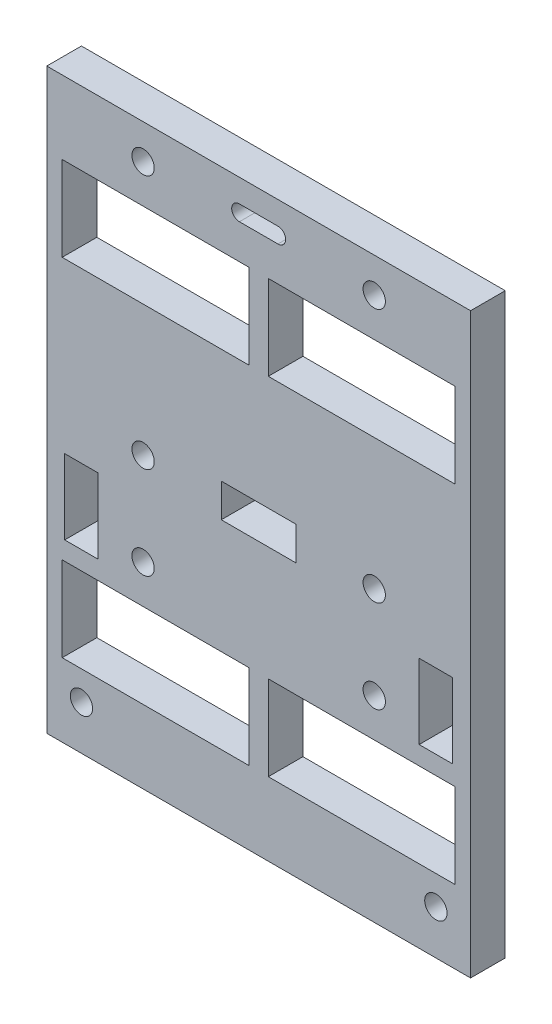
SolidWorks part; units mm, degrees
ref_plane "Front Plane" through (0, 0, 0) normal (0, 0, 1) x (1, 0, 0)
ref_plane "Top Plane" through (0, 0, 0) normal (0, 1, 0) x (1, 0, 0)
ref_plane "Right Plane" through (0, 0, 0) normal (1, 0, 0) x (0, 0, -1)
sketch "Sketch1" plane through (0, 0, 0) normal (0, 0, 1) x (1, 0, 0)
  line L0 (0, -37.5) -> (0, 37.5) construction
  line L1 (-27.5, -37.5) -> (27.5, -37.5)
  line L2 (-27.5, -37.5) -> (-27.5, 37.5)
  line L3 (-27.5, 37.5) -> (27.5, 37.5)
  line L4 (27.5, -37.5) -> (27.5, 37.5)
  line L5 (-27.5, -37.5) -> (27.5, 37.5) construction
  line L6 (-27.5, 37.5) -> (27.5, -37.5) construction
  line L7 (-27.5, 0) -> (27.5, 0) construction
  line L8 (-27.5, 22.5) -> (27.5, 22.5) construction
  line L9 (25.5, 17) -> (1.25, 28) construction
  line L10 (-25.5, 28) -> (-1.25, 28)
  line L11 (-25.5, 28) -> (-25.5, 17)
  line L12 (-25.5, 17) -> (-1.25, 17)
  line L13 (-1.25, 28) -> (-1.25, 17)
  line L14 (-25.5, 28) -> (-1.25, 17) construction
  line L15 (-25.5, 17) -> (-1.25, 28) construction
  line L16 (25.5, 28) -> (1.25, 17) construction
  line L17 (1.25, 28) -> (1.25, 17)
  line L18 (25.5, 17) -> (1.25, 17)
  line L19 (25.5, 28) -> (25.5, 17)
  line L20 (25.5, 28) -> (1.25, 28)
  line L21 (25.5, -28) -> (1.25, -17) construction
  line L22 (-25.5, -17) -> (-1.25, -28) construction
  line L23 (-25.5, -28) -> (-1.25, -17) construction
  line L24 (25.5, -17) -> (1.25, -28) construction
  line L25 (25.5, -28) -> (1.25, -28)
  line L26 (25.5, -28) -> (25.5, -17)
  line L27 (25.5, -17) -> (1.25, -17)
  line L28 (1.25, -28) -> (1.25, -17)
  line L29 (-1.25, -28) -> (-1.25, -17)
  line L30 (-25.5, -17) -> (-1.25, -17)
  line L31 (-25.5, -28) -> (-25.5, -17)
  line L32 (-25.5, -28) -> (-1.25, -28)
  point P0 (0, 0)
  point P12 (-13.375, 22.5)
  point P21 (13.375, 22.5)
  point P30 (13.375, -22.5)
  point P31 (-13.375, -22.5)
  dimension "D1" = 55
  dimension "D2" = 75
  dimension "D3" = 22.5
  dimension "D4" = 24.25
  dimension "D5" = 11
  dimension "D6" = 1.25
extrude "Boss-Extrude1" add sketch "Sketch1" along normal blind 4.5
sketch "Sketch2" plane through (0, 0, 4.5) normal (0, 0, 1) x (1, 0, 0)
  line L0 (0, -37.5) -> (0, 37.5) construction
  line L1 (-27.5, -37.5) -> (27.5, -37.5) construction
  line L2 (27.5, 37.5) -> (-27.5, 37.5) construction
  line L3 (-27.5, 0) -> (27.5, 0) construction
  line L4 (-27.5, 37.5) -> (-27.5, -37.5) construction
  line L5 (27.5, -37.5) -> (27.5, 37.5) construction
  line L6 (-15, 0) -> (15, 0) construction
  circle A0 centre (-15, 33) radius 1.45
  circle A1 centre (15, 33) radius 1.45
  circle A2 centre (15, 0) radius 1.45
  circle A3 centre (-15, 0) radius 1.45
  dimension "D1" = 2.9
  dimension "D7" = 2.9
  dimension "D8" = 2.9
  dimension "D2" = 15
  dimension "D3" = 33
  dimension "D4" = 30
  dimension "D5" = 15
  dimension "D6" = 0
extrude "screwHoles" cut sketch "Sketch2" against normal through all
sketch "Sketch3" plane through (0, 0, 4.5) normal (0, 0, 1) x (1, 0, 0)
  line L0 (-27.5, 9) -> (26.0486, 9) construction
  line L1 (-27.5, 37.5) -> (-27.5, -37.5) construction
  line L3 (0, 37.5) -> (0, -37.5) construction
  line L4 (27.5, 37.5) -> (-27.5, 37.5) construction
  line L5 (-27.5, -37.5) -> (27.5, -37.5) construction
  line L6 (18.95, 6.8) -> (9.05, 11.2) construction
  line L7 (-18.95, 11.2) -> (-9.05, 11.2)
  line L8 (-18.95, 11.2) -> (-18.95, 6.8)
  line L9 (-18.95, 6.8) -> (-9.05, 6.8)
  line L10 (-9.05, 11.2) -> (-9.05, 6.8)
  line L11 (-18.95, 11.2) -> (-9.05, 6.8) construction
  line L12 (-18.95, 6.8) -> (-9.05, 11.2) construction
  line L13 (18.95, 11.2) -> (9.05, 6.8) construction
  line L14 (9.05, 11.2) -> (9.05, 6.8)
  line L15 (18.95, 6.8) -> (9.05, 6.8)
  line L16 (18.95, 11.2) -> (18.95, 6.8)
  line L17 (18.95, 11.2) -> (9.05, 11.2)
  line L18 (-27.5, 37.5) -> (-27.5, -37.5) construction
  point P2 (-27.5, 0)
  point P12 (-14, 9)
  point P21 (14, 9)
  dimension "D1" = 9.9
  dimension "D3" = 14
  dimension "D4" = 9
extrude "BeltClamp" [suppressed] cut sketch "Sketch3" against normal through all
sketch "Sketch4" plane through (0, 0, 4.5) normal (0, 0, 1) x (1, 0, 0)
  line L0 (-27.5, 0) -> (27.5, 0) construction
  line L1 (-27.5, 37.5) -> (-27.5, -37.5) construction
  line L2 (27.5, -37.5) -> (27.5, 37.5) construction
  line L4 (-4.85, 2.175) -> (4.85, 2.175)
  line L5 (-4.85, 2.175) -> (-4.85, -2.175)
  line L6 (-4.85, -2.175) -> (4.85, -2.175)
  line L7 (4.85, 2.175) -> (4.85, -2.175)
  line L8 (-4.85, 2.175) -> (4.85, -2.175) construction
  line L9 (-4.85, -2.175) -> (4.85, 2.175) construction
  circle A0 centre (-15, 0) radius 1.45 construction
  point P6 (0, 0)
  dimension "D2" = 4.35
  dimension "D3" = 0
extrude "mountingPlateTab" cut sketch "Sketch4" against normal through all
sketch "Sketch5" plane through (0, 0, 4.5) normal (0, 0, 1) x (1, 0, 0)
  line L0 (-27.5, -9.75) -> (27.5, -9.75) construction
  line L1 (-27.5, 37.5) -> (-27.5, -37.5) construction
  line L2 (27.5, -37.5) -> (27.5, 37.5) construction
  line L4 (0, -37.5) -> (0, 37.5) construction
  line L5 (-27.5, -37.5) -> (27.5, -37.5) construction
  line L6 (27.5, 37.5) -> (-27.5, 37.5) construction
  line L7 (-20.825, -14.6) -> (-25.175, -4.9) construction
  line L8 (20.825, -4.9) -> (25.175, -4.9)
  line L9 (20.825, -4.9) -> (20.825, -14.6)
  line L10 (20.825, -14.6) -> (25.175, -14.6)
  line L11 (25.175, -4.9) -> (25.175, -14.6)
  line L12 (20.825, -4.9) -> (25.175, -14.6) construction
  line L13 (20.825, -14.6) -> (25.175, -4.9) construction
  line L14 (-20.825, -4.9) -> (-25.175, -14.6) construction
  line L15 (-25.175, -4.9) -> (-25.175, -14.6)
  line L16 (-20.825, -14.6) -> (-25.175, -14.6)
  line L17 (-20.825, -4.9) -> (-20.825, -14.6)
  line L18 (-20.825, -4.9) -> (-25.175, -4.9)
  line L19 (23, -9.75) -> (23, -37.5) construction
  line L20 (-23, -9.75) -> (-23, -37.5) construction
  circle A0 centre (23, -31.75) radius 1.45
  circle A1 centre (-23, -31.75) radius 1.45
  point P15 (23, -9.75)
  point P24 (-23, -9.75)
  dimension "D5" = 2.9
  dimension "D2" = 9.7
  dimension "D3" = 4.35
  dimension "D4" = 23
  dimension "D6" = 22
  dimension "D1" = 9.75
extrude "BraceTabs" cut sketch "Sketch5" against normal through all
sketch "Sketch6" plane through (0, 0, 4.5) normal (0, 0, 1) x (1, 0, 0)
  line L0 (-25.175, -9.75) -> (25.175, -9.75) construction
  line L1 (-25.175, -4.9) -> (-25.175, -14.6) construction
  line L2 (25.175, -14.6) -> (25.175, -4.9) construction
  line L3 (0, -2.175) -> (0, -37.5) construction
  line L4 (-4.85, -2.175) -> (4.85, -2.175) construction
  line L5 (-27.5, -37.5) -> (27.5, -37.5) construction
  line L6 (23, -14.6) -> (23, -4.9) construction
  line L7 (20.825, -14.6) -> (25.175, -14.6) construction
  line L8 (25.175, -4.9) -> (20.825, -4.9) construction
  line L9 (20.825, -4.9) -> (20.825, -14.6) construction
  line L10 (19.825, -15.6) -> (26.175, -15.6)
  line L11 (19.825, -15.6) -> (19.825, -3.9)
  line L12 (19.825, -3.9) -> (26.175, -3.9)
  line L13 (26.175, -15.6) -> (26.175, -3.9)
  line L14 (19.825, -15.6) -> (26.175, -3.9) construction
  line L15 (19.825, -3.9) -> (26.175, -15.6) construction
  line L16 (-19.825, -3.9) -> (-26.175, -15.6) construction
  line L17 (-19.825, -15.6) -> (-26.175, -3.9) construction
  line L18 (-23, -14.6) -> (-23, -4.9) construction
  line L19 (-26.175, -15.6) -> (-26.175, -3.9)
  line L20 (-19.825, -3.9) -> (-26.175, -3.9)
  line L21 (-19.825, -15.6) -> (-19.825, -3.9)
  line L22 (-19.825, -15.6) -> (-26.175, -15.6)
  circle A0 centre (23, -9.75) radius 1.45
  circle A1 centre (-23, -9.75) radius 1.45
  point P18 (23, -9.75)
  dimension "D3" = 2.9
  dimension "D1" = 1
  dimension "D2" = 1
extrude "FrontToRear1" [suppressed] add sketch "Sketch6" against normal up to surface (4.5 mm away) up to face at (-24.45, -31.75, 0)
sketch "Sketch7" plane through (0, 0, 4.5) normal (0, 0, 1) x (1, 0, 0)
  line L0 (4.85, 2.175) -> (-4.85, 2.175) construction
  line L1 (-20, -3.175) -> (20, -3.175)
  line L2 (-20, -3.175) -> (-20, 3.175)
  line L3 (-20, 3.175) -> (20, 3.175)
  line L4 (20, -3.175) -> (20, 3.175)
  line L5 (-20, -3.175) -> (20, 3.175) construction
  line L6 (-20, 3.175) -> (20, -3.175) construction
  circle A0 centre (15, 0) radius 1.45 construction
  point P0 (0, 0)
  dimension "D1" = 1
  dimension "D2" = 5
extrude "FrontToRear2" [suppressed] add sketch "Sketch7" against normal through all
sketch "Sketch8" plane through (0, 0, 4.5) normal (0, 0, 1) x (1, 0, 0)
  line L0 (-27.5, -12) -> (27.5, -12) construction
  line L1 (-27.5, 37.5) -> (-27.5, -37.5) construction
  line L2 (27.5, -37.5) -> (27.5, 37.5) construction
  line L3 (0, -37.5) -> (0, 0) construction
  line L4 (-27.5, -37.5) -> (27.5, -37.5) construction
  circle A0 centre (-15, -12) radius 1.45
  circle A1 centre (15, -12) radius 1.45
  dimension "D2" = 2.9
  dimension "D1" = 12
  dimension "D3" = 15
extrude "ExpansionScrewholes" cut sketch "Sketch8" against normal through all
sketch "Sketch12" plane through (0, 0, 4.5) normal (0, 0, 1) x (1, 0, 0)
  line L0 (0, 37.5) -> (0, 0) construction
  line L1 (27.5, 37.5) -> (-27.5, 37.5) construction
  line L2 (-2.5, 33.5) -> (2.5, 33.5) construction
  line L3 (-2.5, 34.5) -> (2.5, 34.5)
  line L4 (-2.5, 32.5) -> (2.5, 32.5)
  arc A0 (-2.5, 34.5) -> (-2.5, 32.5) centre (-2.5, 33.5) ccw
  arc A1 (2.5, 32.5) -> (2.5, 34.5) centre (2.5, 33.5) ccw
  point P7 (0, 33.5)
  dimension "D1" = 3
  dimension "D2" = 2
  dimension "D3" = 5
extrude "CableTieSlot" cut sketch "Sketch12" against normal through all
sketch "Sketch11" [suppressed] plane through (0, 0, 4.5) normal (0, 0, 1) x (1, 0, 0)
  line L0 (13.5615, -8.85) -> (27.5, -8.85) construction
  line L1 (27.5, -37.5) -> (27.5, 37.5) construction
  line L2 (0, 37.5) -> (0, -37.5) construction
  line L3 (36.5, -14.85) -> (18.5, -14.85)
  line L4 (36.5, -14.85) -> (36.5, -2.85)
  line L5 (36.5, -2.85) -> (18.5, -2.85)
  line L6 (18.5, -14.85) -> (18.5, -2.85)
  line L7 (36.5, -14.85) -> (18.5, -2.85) construction
  line L8 (36.5, -2.85) -> (18.5, -14.85) construction
  line L11 (-36.5, -2.85) -> (-18.5, -14.85) construction
  line L12 (-36.5, -14.85) -> (-18.5, -2.85) construction
  line L13 (-18.5, -14.85) -> (-18.5, -2.85)
  line L14 (-36.5, -2.85) -> (-18.5, -2.85)
  line L15 (-36.5, -14.85) -> (-36.5, -2.85)
  line L16 (-36.5, -14.85) -> (-18.5, -14.85)
  line L17 (36.5, -2.85) -> (18.5, -14.85) construction
  line L18 (20.65, -14.85) -> (25.35, -14.85) construction
  line L19 (27.5, 37.5) -> (-27.5, 37.5) construction
  line L20 (-27.5, -37.5) -> (27.5, -37.5) construction
  dimension "D1" = 9
  dimension "D2" = 12
  dimension "D3" = 0
extrude "Cut-Extrude2" [suppressed] cut sketch "Sketch11" against normal through all
sketch "Sketch10" plane through (0, 0, 4.5) normal (0, 0, 1) x (1, 0, 0)
  line L0 (4.7446, 1) -> (27.5, 1) construction
  line L1 (-4.85, 0) -> (4.85, 0) construction
  line L2 (27.5, -37.5) -> (27.5, 37.5) construction
  line L3 (0, 2.175) -> (0, -2.175) construction
  line L4 (36.5, 4) -> (18.5, 4)
  line L5 (36.5, 4) -> (36.5, -2)
  line L6 (36.5, -2) -> (18.5, -2)
  line L7 (18.5, 4) -> (18.5, -2)
  line L8 (36.5, 4) -> (18.5, -2) construction
  line L9 (36.5, -2) -> (18.5, 4) construction
  line L10 (4.85, 2.175) -> (-4.85, 2.175) construction
  line L11 (-4.85, -2.175) -> (4.85, -2.175) construction
  line L12 (-36.5, -2) -> (-18.5, 4) construction
  line L13 (-36.5, 4) -> (-18.5, -2) construction
  line L14 (-4.7446, 1) -> (-27.5, 1) construction
  line L15 (-18.5, 4) -> (-18.5, -2)
  line L16 (-36.5, -2) -> (-18.5, -2)
  line L17 (-36.5, 4) -> (-36.5, -2)
  line L18 (-36.5, 4) -> (-18.5, 4)
  line L19 (36.5, -2) -> (18.5, 4) construction
  line L20 (-4.85, 2.175) -> (-4.85, -2.175) construction
  line L21 (4.85, -2.175) -> (4.85, 2.175) construction
  dimension "D1" = 6
  dimension "D2" = 9
  dimension "D3" = 1
extrude "CableTieSlots" [suppressed] cut sketch "Sketch10" against normal through all
sketch "Sketch9" [suppressed] plane through (0, 0, 4.5) normal (0, 0, 1) x (1, 0, 0)
  line L0 (-27.5, -37.5) -> (27.5, -37.5) construction
  line L5 (-9, -42.5) -> (9, -42.5)
  line L6 (-9, -42.5) -> (-9, -34.5)
  line L7 (-7, -32.5) -> (7, -32.5)
  line L8 (9, -42.5) -> (9, -34.5)
  line L9 (-9, -42.5) -> (9, -32.5) construction
  line L10 (-9, -32.5) -> (9, -42.5) construction
  arc A0 (7, -32.5) -> (9, -34.5) centre (7, -34.5) cw
  arc A1 (-9, -34.5) -> (-7, -32.5) centre (-7, -34.5) cw
  point P9 (0, -37.5)
  dimension "D3" = 2
  dimension "D1" = 18
  dimension "D2" = 5
extrude "RearFanSlot" [suppressed] cut sketch "Sketch9" against normal through all
sketch "Sketch13" [suppressed] plane through (0, 0, 4.5) normal (0, 0, 1) x (1, 0, 0)
  line L1 (-7, -2.85) -> (7, -2.85)
  line L2 (-7, -2.85) -> (-7, -11.85)
  line L3 (-7, -11.85) -> (7, -11.85)
  line L4 (7, -2.85) -> (7, -11.85)
  line L5 (-7, -2.85) -> (7, -11.85) construction
  line L6 (-7, -11.85) -> (7, -2.85) construction
  line L9 (0, 37.5) -> (0, -7.35) construction
  line L10 (-18.5, -2.85) -> (-27.5, -2.85) construction
  line L11 (27.5, 37.5) -> (-27.5, 37.5) construction
  line L13 (-27.5, -14.85) -> (-18.5, -14.85) construction
  point P0 (0, -7.35)
  dimension "D1" = 3
  dimension "D2" = 0
  dimension "D3" = 7
extrude "Cut-Extrude3" [suppressed] cut sketch "Sketch13" against normal through all
sketch "Sketch14" [suppressed] plane through (0, 0, 4.5) normal (0, 0, 1) x (1, 0, 0)
  line L0 (25.2, -4.85) -> (20.8, -4.85) construction
  line L1 (25.2, -4.85) -> (20.8, -4.85)
  line L2 (25.2, -4.85) -> (25.2, -14.65)
  line L3 (25.2, -14.65) -> (20.8, -14.65)
  line L4 (20.8, -4.85) -> (20.8, -14.65)
  line L5 (25.2, -14.65) -> (25.2, -4.85) construction
  line L6 (0, 0) -> (0, -6.835) construction
  line L7 (-20.8, -4.85) -> (-20.8, -14.65)
  line L8 (-25.2, -14.65) -> (-20.8, -14.65)
  line L9 (-25.2, -4.85) -> (-25.2, -14.65)
  line L10 (-25.2, -4.85) -> (-20.8, -4.85)
extrude "Boss-Extrude2" [suppressed] add sketch "Sketch14" against normal through all
equation "\"X-ROD-SPACING\"=45"
equation "\"Y-ROD-SPACING\"=75"
equation "\"Z-ROD-SPACING\"=17.5"
equation "\"Y-BED-OFFSET\"=2"
equation "\"Y-BED-ROD-INSET\"=3.5"
equation "\"Y-BED-SCREW-SPACING\"=209"
equation "\"Y-BED-SCREW-CUTOUT-SLOT-HEIGHT\"=2"
equation "\"T-SLOT-NUT-FILLET-RADIUS\"=0.5"
equation "\"T-SLOT-SCREW-SHAFT-RADIUS\"=1.55"
equation "\"T-SLOT-SCREW-SHAFT-CUTOUT-LENGTH\"=11"
equation "\"T-SLOT-NUT-DEPTH\"=3.5"
equation "\"T-SLOT-NUT-WIDTH\"=2.85"
equation "\"T-SLOT-NUT-END-DISTANCE\"=8"
equation "\"ACRYLIC-THICKNESS\"=10"
equation "\"ACRYLIC-THICKNESS2\"=4.5"
equation "\"ACRYLIC-TAB-CUTOUT-SIZE\"=\"ACRYLIC-THICKNESS\"+\"ACRYLIC-TAB-TOLERANCE\"*2"
equation "\"ACRYLIC-TAB-WIDTH\"=\"ACRYLIC-THICKNESS\""
equation "\"ACRYLIC-M3-HOLE\"=2.9"
equation "\"SMOOTHROD-CAP-SCREW-DISTANCE\"=20"
equation "\"FRAME-WIDTH-INNER\"=370"
equation "\"NEMA17-HOLE-SPACING\"=31"
equation "\"NEMA17-CENTRAL-CUTOUT\"=22.5"
equation "\"Z-BRACKET-REACH\"=57"
equation "\"Z-ROD-INSET\"=13.5"
equation "\"TOP-BRACKET-SPACING\"=40"
equation "\"SMOOTHROD-X-LENGTH\"=350"
equation "\"SMOOTHROD-Y-LENGTH\"=350"
equation "\"SMOOTHROD-Z-LENGTH\"=350"
equation "\"SMOOTHROD-TIGHTENING-HEADROOM\"=.25"
equation "\"LEADSCREW-Z-LENGTH\"=300"
equation "\"SCREW-LENGTH-FRAME\"=\"ACRYLIC-THICKNESS\" + 10"
equation "\"SCREW-LENGTH-MOTOR\"=\"ACRYLIC-THICKNESS\" + 5"
equation "\"SCREW-HEAD-RADIUS\"=6"
equation "\"PRINTED-X-SMOOTHROD-DIAMETER\"=8.8"
equation "\"PRINTED-X-SMOOTHROD-CUTOUT\"=10"
equation "\"PRINTED-X-BASE-HEIGHT\"=10"
equation "\"PRINTED-LM8UU-CUTOUT-SIZE\"=15.5"
equation "\"PRINTED-LM8UU-CUTOUT-LENGTH\"=24.5"
equation "\"PRINTED-X-IDLER-HEIGHT\"=16"
equation "\"PSU-MOUNTING-WIDTH\"=95"
equation "\"PSU-MOUNTING-HEIGHT\"=177"
equation "\"Y-BELT-TO-ROD-DISTANCE\"=20"
equation "\"SPOOL-HOLDER-ROD-SPACING\"=150"
equation "\"D3@Sketch1\"=\"X-ROD-SPACING\"/2"
equation "\"D4@Sketch1\"=\"ACRYLIC-X-CARRIAGE-LM8UU-CUTOUT-WIDTH\""
equation "\"D1@Boss-Extrude1\"=\"ACRYLIC-THICKNESS2\""
equation "\"D1@Sketch2\"=\"ACRYLIC-M3-HOLE\""
equation "\"D1@Sketch3\"=\"ACRYLIC-TAB-CUTOUT-SIZE\""
equation "\"D2@Sketch3\"=\"ACRYLIC-THICKNESS2\"+\"ACRYLIC-TAB-TOLERANCE\"*2"
equation "\"ACRYLIC-X-CARRIAGE-WIDTH\"=55"
equation "\"ACRYLIC-X-CARRIAGE-HEIGHT\"=75"
equation "\"D1@Sketch1\"=\"ACRYLIC-X-CARRIAGE-WIDTH\""
equation "\"D2@Sketch1\"=\"ACRYLIC-X-CARRIAGE-HEIGHT\""
equation "\"ACRYLIC-X-CARRIAGE-CENTER-TAB-SPACING\"=14"
equation "\"D3@Sketch3\"=\"ACRYLIC-X-CARRIAGE-CENTER-TAB-SPACING\""
equation "\"SCREW-LENGTH-EXTRUDER\"=28"
equation "\"ACRYLIC-X-CARRIAGE-SCREW-SPACING-X\"=15"
equation "\"ACRYLIC-X-CARRIAGE-SCREW-SPACING-Y\"=33"
equation "\"D2@Sketch2\"=\"ACRYLIC-X-CARRIAGE-SCREW-SPACING-X\""
equation "\"D3@Sketch2\"=\"ACRYLIC-X-CARRIAGE-SCREW-SPACING-Y\""
equation "\"D1@Sketch4\"=\"ACRYLIC-TAB-WIDTH\"-\"KERF\"*4"
equation "\"D2@Sketch4\"=\"ACRYLIC-THICKNESS2\"-\"KERF\"*2"
equation "\"D2@Sketch5\"=\"ACRYLIC-TAB-WIDTH\"-\"KERF\"*4"
equation "\"D3@Sketch5\"=\"ACRYLIC-THICKNESS2\"-\"KERF\"*2"
equation "\"ACRYLIC-X-CARRIAGE-EXTRUDER-SHELF-DEPTH\"=\"ACRYLIC-X-CARRIAGE-EXTRUDER-OFFSET\" + 28"
equation "\"ACRYLIC-X-CARRIAGE-EXTRUDER-BRACE-SPACING\"=23"
equation "\"D4@Sketch5\"=\"ACRYLIC-X-CARRIAGE-EXTRUDER-BRACE-SPACING\""
equation "\"D4@Sketch2\"=\"ACRYLIC-X-CARRIAGE-SCREW-SPACING-X\"*2"
equation "\"D5@Sketch2\"=\"ACRYLIC-X-CARRIAGE-SCREW-SPACING-X\""
equation "\"D7@Sketch2\"=\"ACRYLIC-M3-HOLE\""
equation "\"D8@Sketch2\"=\"ACRYLIC-M3-HOLE\""
equation "\"ACRYLIC-X-CARRIAGE-LM8UU-CUTOUT-WIDTH\"=24.25"
equation "\"ACRYLIC-TAB-TOLERANCE\"=-.05"
equation "\"ACRYLIC-X-CARRIAGE-EXTRUDER-OFFSET\"=26"
equation "\"ACRYLIC-X-CARRIAGE-EXTRUDER-ANGLE\"=90"
equation "\"ACRYLIC-X-CARRIAGE-EXTRUDER-BRACE-TAB-OFFSET\"=20"
equation "\"ACRYLIC-X-CARRIAGE-EXTRUDER-BRACE-HEIGHT\"=35"
equation "\"ACRYLIC-X-CARRIAGE-EXTRUDER-BRACE-SCREW-SPACING\"=22"
equation "\"D5@Sketch5\"=\"ACRYLIC-M3-HOLE\""
equation "\"D3@Sketch6\"=\"ACRYLIC-M3-HOLE\""
equation "\"ACRYLIC-X-CARRIAGE-LM8UU-CUTOUT-HEIGHT\"=11.0"
equation "\"ACRYLIC-X-CARRIAGE-DUAL-WIDTH-MULTIPLIER\"=1.65"
equation "\"ACRYLIC-X-CARRIAGE-DUAL-HOTEND-SPACING\"=42"
equation "\"ACRYLIC-X-CARRIAGE-DUAL-WIDTH\"=75"
equation "\"ACRYLIC-X-CARRIAGE-DUAL-HOTEND-SEPARATION\"=36"
equation "\"ACRYLIC-X-CARRIAGE-DUAL-MOUNT-PLATE-DEPTH\"=75"
equation "\"ACRYLIC-X-CARRIAGE-DUAL-MOUNT-BRACE-WIDTH\"=33"
equation "\"ACRYLIC-X-CARRIAGE-DUAL-MOUNT-SCREW-WIDTH\"=40"
equation "\"D5@Sketch1\"=\"ACRYLIC-X-CARRIAGE-LM8UU-CUTOUT-HEIGHT\""
equation "\"D2@Sketch8\"=\"ACRYLIC-M3-HOLE\""
equation "\"D1@Sketch5\"=\"ACRYLIC-THICKNESS2\"/2 + 7.5"
equation "\"KERF\"=0.075"
equation "\"PRINTED-M3-HOLE\"=3.5"
equation "\"PRINTED-M3-NUT-AF\"=6.25"
equation "\"ACRYLIC-X-CARRIAGE-DUAL-FAN-OFFSET\"=52"
equation "\"ACRYLIC-X-CARRIAGE-DUAL-FAN-HEIGHT\"=20"
equation "\"BLOWER-FAN-WIDTH\"=15"
